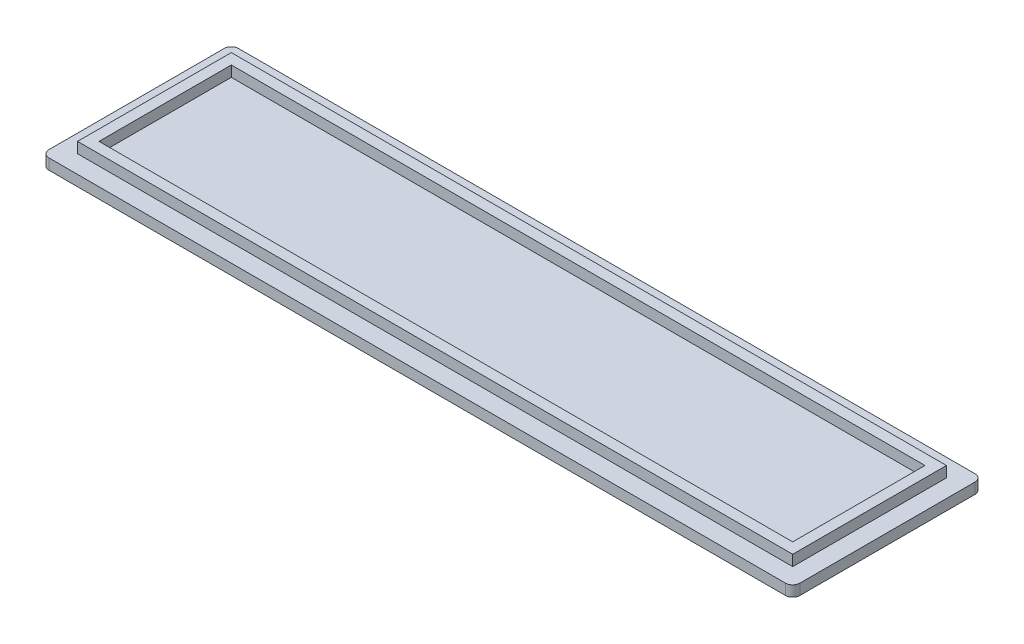
SolidWorks part; units mm, degrees
material "PET"
ref_plane "Спереди" through (0, 0, 0) normal (0, 0, 1) x (1, 0, 0)
ref_plane "Сверху" through (0, 0, 0) normal (0, 1, 0) x (1, 0, 0)
ref_plane "Справа" through (0, 0, 0) normal (1, 0, 0) x (0, 0, -1)
other "Configuration Table"
sketch "Основание & крышка" plane through (0, 0, 0) normal (0, 1, 0) x (1, 0, 0)
  line L1 (105, -26.5) -> (-105, -26.5)
  line L2 (105, -26.5) -> (105, 26.5)
  line L3 (105, 26.5) -> (-105, 26.5)
  line L4 (-105, -26.5) -> (-105, 26.5)
  line L5 (105, -26.5) -> (-105, 26.5) construction
  line L6 (105, 26.5) -> (-105, -26.5) construction
  line L7 (100, -21.5) -> (-100, -21.5)
  line L8 (100, -21.5) -> (100, 21.5)
  line L9 (100, 21.5) -> (-100, 21.5)
  line L10 (-100, -21.5) -> (-100, 21.5)
  line L11 (100, -21.5) -> (-100, 21.5) construction
  line L12 (100, 21.5) -> (-100, -21.5) construction
  point P0 (0, 0)
  point P5 (0, 0)
  dimension "D1" = 210
  dimension "D2" = 53
  dimension "D3" = 43
  dimension "D4" = 200
extrude "Бобышка-Вытянуть1" add sketch "Основание & крышка" along normal blind 50 contours L3 L4 L1 L2
sketch "Эскиз3" plane through (0, 0, 0) normal (0, -1, 0) x (1, 0, 0)
  line L0 (105, 26.5) -> (-105, 26.5) construction
  line L1 (-100, -21.5) -> (100, -21.5)
  line L2 (-100, -21.5) -> (-100, 21.5)
  line L3 (-100, 21.5) -> (100, 21.5)
  line L4 (100, -21.5) -> (100, 21.5)
  line L5 (-100, -21.5) -> (100, 21.5) construction
  line L6 (-100, 21.5) -> (100, -21.5) construction
  line L7 (105, 26.5) -> (105, -26.5) construction
  point P0 (0, 0)
  dimension "D1" = 5
  dimension "D2" = 5
extrude "Вырез-Вытянуть1" cut sketch "Эскиз3" against normal blind 45
sketch "Эскиз4" plane through (0, 50, 0) normal (0, 1, 0) x (1, 0, 0)
  line L0 (0, 41.131) -> (0, -55.5904) construction
  line L1 (105, 26.5) -> (-105, 26.5) construction
  line L2 (105, -26.5) -> (105, 26.5) construction
  line L3 (-127.2033, 0) -> (126.8125, 0) construction
  circle A0 centre (98, 19.5) radius 3.5
  circle A1 centre (-98, 19.5) radius 3.5
  circle A2 centre (98, -19.5) radius 3.5
  circle A3 centre (-98, -19.5) radius 3.5
  dimension "D1" = 7
  dimension "D3" = 7
  dimension "D2" = 7
sketch "Эскиз6" plane through (0, 50, 0) normal (0, 1, 0) x (1, 0, 0)
  line L0 (-117.6289, 0) -> (122.9046, 0) construction
  line L1 (0, 47.7745) -> (0, -57.5444) construction
extrude "Бобышка-Вытянуть2" add sketch "Эскиз4" along normal blind 2 draft 1 contours A0
fillet "Скругление2" radius 0.5 1 edges at (98, 52, -16.0349)
extrude "Бобышка-Вытянуть3" add sketch "Эскиз4<5>" along normal blind 2 contours A2
sketch "Эскиз4<5>" plane through (0, 50, 0) normal (0, 1, 0) x (1, 0, 0) same geometry as "Эскиз4"
extrude "Бобышка-Вытянуть4" add sketch "Эскиз4<6>" along normal blind 2 contours A3
sketch "Эскиз4<6>" plane through (0, 50, 0) normal (0, 1, 0) x (1, 0, 0) same geometry as "Эскиз4"
extrude "Бобышка-Вытянуть5" add sketch "Эскиз4<7>" along normal blind 2 contours A1
sketch "Эскиз4<7>" plane through (0, 50, 0) normal (0, 1, 0) x (1, 0, 0) same geometry as "Эскиз4"
fillet "Скругление3" radius 0.5 1 edges at (-98, 52, 23)
fillet "Скругление4" radius 0.5 1 edges at (-98, 52, -23)
fillet "Скругление5" radius 0.5 1 edges at (98, 52, 16)
sketch "Эскиз7" plane through (0, 0, -26.5) normal (0, 0, -1) x (-1, 0, 0)
  line L0 (0, -32.9698) -> (0, 82.1336) construction
  line L1 (-136.416, 24.5819) -> (136.5704, 24.5819) construction
  circle A0 centre (0, 35.0819) radius 6
  point P7 (0, 24.5819)
  dimension "D1" = 12
  dimension "D2" = 10.5
extrude "Вырез-Вытянуть2" cut sketch "Эскиз7" against normal blind 14 draft 5 contours A0
fillet "Скругление6" radius 2 1 edges at (-6, 35.0819, -26.5)
sketch "Эскиз8" plane through (0, 0, -21.5) normal (0, 0, 1) x (1, 0, 0)
  circle A0 centre (0, 35.0819) radius 7
  dimension "D1" = 14
extrude "Бобышка-Вытянуть6" add sketch "Эскиз8" along normal blind 7 draft 5 contours A0
sketch "Эскиз9" plane through (0, 0, -14.5) normal (0, 0, 1) x (1, 0, 0)
  circle A0 centre (0, 35.0819) radius 5.15
  dimension "D1" = 10.3
extrude "Вырез-Вытянуть3" cut sketch "Эскиз9" against normal blind 7 draft 5 draft outward yes
sketch "Эскиз10" plane through (0, 0, 26.5) normal (0, 0, 1) x (1, 0, 0)
  line L0 (0, -14.7722) -> (0, 61.6389) construction
  line L1 (-118.5615, 25) -> (116.6086, 25) construction
  line L2 (-127.2033, 50) -> (126.8125, 50) construction
  line L3 (-64.7, 38.15) -> (-35.3, 38.15)
  line L4 (-64.7, 38.15) -> (-64.7, 11.85)
  line L5 (-64.7, 11.85) -> (-35.3, 11.85)
  line L6 (-35.3, 38.15) -> (-35.3, 11.85)
  line L7 (-64.7, 38.15) -> (-35.3, 11.85) construction
  line L8 (-64.7, 11.85) -> (-35.3, 38.15) construction
  point P5 (-50, 25)
  point P13 (0, 25)
  dimension "D1" = 29.4
  dimension "D2" = 26.3
  dimension "D3" = 50
  dimension "D4" = 25
extrude "Вырез-Вытянуть4" cut sketch "Эскиз10" against normal blind 5
sketch "Эскиз13" plane through (0, 0, 21.5) normal (0, 0, -1) x (-1, 0, 0)
  line L0 (100, 45) -> (100, 0) construction
  line L1 (30.4, 38.75) -> (69.6, 38.75)
  line L2 (30.4, 38.75) -> (30.4, 11.25)
  line L3 (30.4, 11.25) -> (69.6, 11.25)
  line L4 (69.6, 38.75) -> (69.6, 11.25)
  line L5 (30.4, 38.75) -> (69.6, 11.25) construction
  line L6 (30.4, 11.25) -> (69.6, 38.75) construction
  line L8 (-100, 45) -> (100, 45) construction
  point P0 (50, 25)
  dimension "D1" = 50
  dimension "D2" = 20
  dimension "D3" = 27.5
  dimension "D4" = 39.2
extrude "Вырез-Вытянуть5" cut sketch "Эскиз13" against normal blind 2
sketch "Эскиз14" plane through (0, 0, 26.5) normal (0, 0, 1) x (1, 0, 0)
  line L0 (0, 0) -> (0, 50) construction
  line L1 (105, 0) -> (-105, 0) construction
  line L2 (105, 50) -> (-105, 50) construction
  line L3 (-105, 25) -> (105, 25) construction
  line L4 (-105, 50) -> (-105, 0) construction
  line L5 (105, 50) -> (105, 0) construction
  line L6 (-79.5, 28.8) -> (-73.5, 28.8)
  line L7 (-79.5, 15.2) -> (-73.5, 15.2)
  line L8 (-79.5, 15.2) -> (-79.5, 21.2)
  line L9 (-79.5, 21.2) -> (-73.5, 21.2)
  line L10 (-73.5, 15.2) -> (-73.5, 21.2)
  line L11 (-79.5, 15.2) -> (-73.5, 21.2) construction
  line L12 (-79.5, 21.2) -> (-73.5, 15.2) construction
  line L13 (-79.5, 28.8) -> (-73.5, 34.8) construction
  line L14 (-79.5, 34.8) -> (-79.5, 28.8)
  line L15 (-79.5, 34.8) -> (-73.5, 28.8) construction
  line L16 (-73.5, 34.8) -> (-73.5, 28.8)
  line L17 (-79.5, 34.8) -> (-73.5, 34.8)
  point P12 (-76.5, 18.2)
  point P21 (-76.5, 31.8)
  dimension "D1" = 6
  dimension "D2" = 6
  dimension "D3" = 18.2
  dimension "D4" = 25.5
extrude "Вырез-Вытянуть6" cut sketch "Эскиз14" against normal blind 5
sketch "Эскиз16" plane through (0, 0, 21.5) normal (0, 0, -1) x (-1, 0, 0)
  line L0 (-100, 45) -> (100, 45) construction
  line L1 (73.4, 34.85) -> (79.5, 34.85)
  line L2 (73.4, 34.85) -> (73.4, 28.75)
  line L3 (73.4, 28.75) -> (79.5, 28.75)
  line L4 (79.5, 34.85) -> (79.5, 28.75)
  line L5 (73.4, 34.85) -> (79.5, 28.75) construction
  line L6 (73.4, 28.75) -> (79.5, 34.85) construction
  line L7 (100, 45) -> (100, 0) construction
  point P0 (76.45, 31.8)
  dimension "D1" = 6.1
  dimension "D2" = 6.1
  dimension "D3" = 13.2
  dimension "D4" = 20.5
fillet "Скругление7" radius 2 8 edges at (-105, 25, -26.5) (-105, 50, 0) (0, 50, -26.5) (105, 25, -26.5) (105, 50, 0) (105, 25, 26.5) (-105, 25, 26.5) (0, 50, 26.5)
sketch "Эскиз17" plane through (0, 0, 0) normal (0, -1, 0) x (1, 0, 0)
  line L4 (-105, 24.5) -> (-105, -24.5)
  line L5 (-103, -26.5) -> (103, -26.5)
  line L6 (105, -24.5) -> (105, 24.5)
  line L7 (103, 26.5) -> (-103, 26.5)
  line L8 (-105, 24.5) -> (-105, -24.5)
  line L9 (-103, -26.5) -> (103, -26.5)
  line L10 (105, -24.5) -> (105, 24.5)
  line L11 (103, 26.5) -> (-103, 26.5)
  arc A4 (-105, -24.5) -> (-103, -26.5) centre (-103, -24.5) ccw
  arc A5 (103, -26.5) -> (105, -24.5) centre (103, -24.5) ccw
  arc A6 (105, 24.5) -> (103, 26.5) centre (103, 24.5) ccw
  arc A7 (-103, 26.5) -> (-105, 24.5) centre (-103, 24.5) ccw
  arc A8 (-105, -24.5) -> (-103, -26.5) centre (-103, -24.5) ccw
  arc A9 (103, -26.5) -> (105, -24.5) centre (103, -24.5) ccw
  arc A10 (105, 24.5) -> (103, 26.5) centre (103, 24.5) ccw
  arc A11 (-103, 26.5) -> (-105, 24.5) centre (-103, 24.5) ccw
  dimension "D1" = 0
extrude "Бобышка-Вытянуть8" add sketch "Эскиз17" along normal blind 3 separate body
sketch "Эскиз18" plane through (0, 0, 0) normal (0, 1, 0) x (1, 0, 0)
  line L8 (-100, -21.5) -> (100, -21.5)
  line L28 (-100, -21.5) -> (100, -21.5)
  line L32 (100, -21.5) -> (100, 21.5)
  line L34 (100, -21.5) -> (100, 21.5)
  line L36 (100, 21.5) -> (-100, 21.5)
  line L37 (100, 21.5) -> (-100, 21.5)
  line L38 (-100, 21.5) -> (-100, -21.5)
  line L39 (-100, 21.5) -> (-100, -21.5)
  dimension "D1" = 5
extrude "Крышка" add sketch "Эскиз18" along normal blind 3 from surface thin contours L37 L39 L28 L34 starting at face at (0, 0, 0) thin type one direction reverse wall 3
sketch "Эскиз20" plane through (0, -3, 0) normal (0, -1, 0) x (1, 0, 0)
  line L0 (-105, 0) -> (105, 0) construction
  line L1 (-105, 24.5) -> (-105, -24.5) construction
  line L2 (105, -24.5) -> (105, 24.5) construction
  line L3 (0, 26.5) -> (0, -26.5) construction
  line L4 (103, 26.5) -> (-103, 26.5) construction
  line L5 (-103, -26.5) -> (103, -26.5) construction
sketch "Эскиз21" plane through (0, -3, 0) normal (0, -1, 0) x (1, 0, 0)
  line L0 (-66.7, -49.4791) -> (-66.7, 41.6381) construction
  line L1 (-33.4, -45.2678) -> (-33.4, 45.8494) construction
  line L2 (33.4, -44.7574) -> (33.4, 46.3598) construction
  line L3 (66.7, -45.7783) -> (66.7, 45.3389) construction
  line L4 (105, -24.5) -> (105, 24.5) construction
  line L5 (0, 26.5) -> (0, -26.5) construction
  line L6 (0, -41.131) -> (0, 55.5904) construction
  line L7 (10.5, 60.8548) -> (10.5, -34.3859) construction
  line L12 (103, 26.5) -> (-103, 26.5) construction
  line L13 (8.45, 15.8) -> (12.55, 15.8)
  line L26 (8.45, 15.8) -> (8.45, 18)
  line L27 (8.45, 18) -> (12.55, 18)
  line L28 (12.55, 15.8) -> (12.55, 18)
  line L45 (8.45, 15.8) -> (12.55, 18) construction
  line L46 (8.45, 18) -> (12.55, 15.8) construction
  line L63 (14.5, 51.6017) -> (14.5, -2.5243) construction
  line L64 (20.55, 18) -> (16.45, 15.8) construction
  line L77 (20.55, 15.8) -> (16.45, 18) construction
  line L78 (16.45, 15.8) -> (16.45, 18)
  line L79 (20.55, 18) -> (16.45, 18)
  line L80 (20.55, 15.8) -> (20.55, 18)
  line L81 (20.55, 15.8) -> (16.45, 15.8)
  line L198 (0, 55.5904) -> (0, -41.131) construction
  point P14 (10.5, 16.9)
  point P21 (10.5, 18)
  point P28 (18.5, 16.9)
  dimension "D1" = 38.3
  dimension "D2" = 33.3
  dimension "D3" = 33.4
  dimension "D4" = 33.4
  dimension "D5" = 33.3
  dimension "D6" = 10.5
  dimension "D7" = 4.1
  dimension "D8" = 2.2
  dimension "D9" = 2.2
  dimension "D10" = 4
  dimension "D11" = 8.5
delete or keep bodies "Тело-Удалить/Сохранить 1" type keep bodies bodies 126
extrude "Вырез-Вытянуть7" cut sketch "Эскиз21" against normal blind 3
